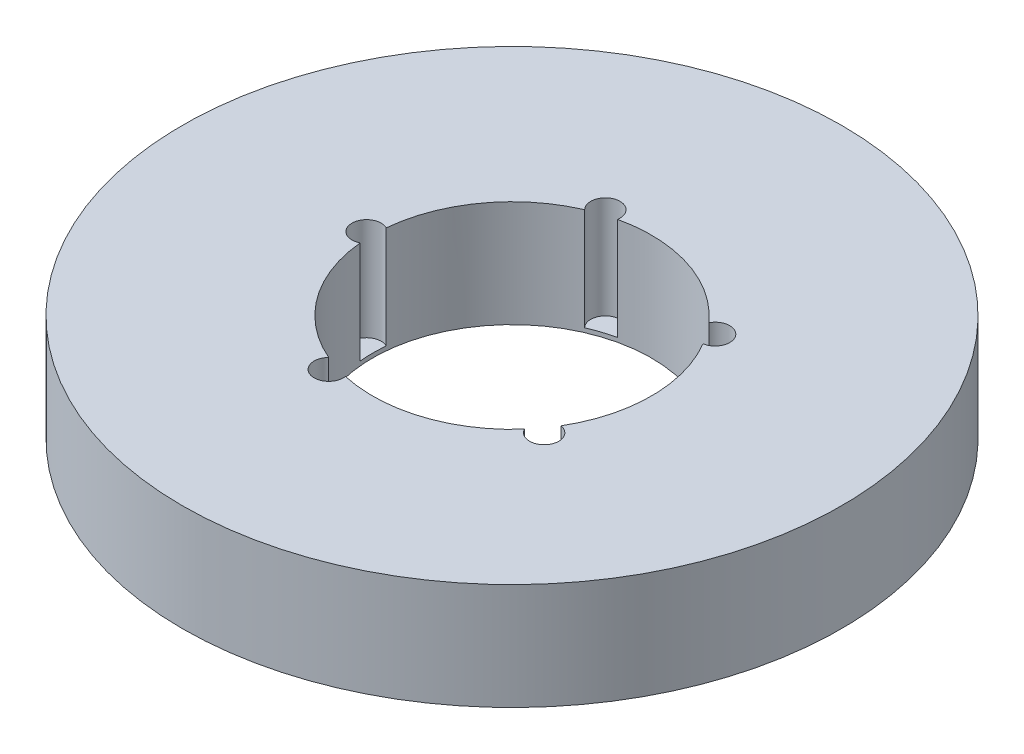
SolidWorks part; units mm, degrees
ref_plane "Front Plane" through (0, 0, 0) normal (0, 0, 1) x (1, 0, 0)
ref_plane "Top Plane" through (0, 0, 0) normal (0, 1, 0) x (1, 0, 0)
ref_plane "Right Plane" through (0, 0, 0) normal (1, 0, 0) x (0, 0, -1)
sketch "Sketch1" plane through (0, 0, 0) normal (0, 1, 0) x (1, 0, 0)
  circle A0 centre (0, 0) radius 65
  dimension "FLANGE_OD" = 130
extrude "Boss-Extrude1" add sketch "Sketch1" along normal blind 21
sketch "Sketch2" plane through (0, 0, 0) normal (0, 1, 0) x (1, 0, 0)
  circle A0 centre (0, 0) radius 27.5
  dimension "BORE_D" = 55
extrude "Cut-Extrude1" cut sketch "Sketch2" along normal through all
sketch "Sketch3" plane through (0, 21, 0) normal (0, 1, 0) x (1, 0, 0)
  circle A0 centre (0, 0) radius 28.6847 construction
  circle A1 centre (-28.6847, 0) radius 2.8853
  dimension "BOLT_D" = 5.7706
  dimension "BOLT_PCD" = 57.3694
extrude "Cut-Extrude2" cut sketch "Sketch3" against normal blind 20.1738
pattern_circular "CirPattern1" count 5 over 360 about axis through (0, 0, 0) along (0, 1, 0) of "Cut-Extrude2"
